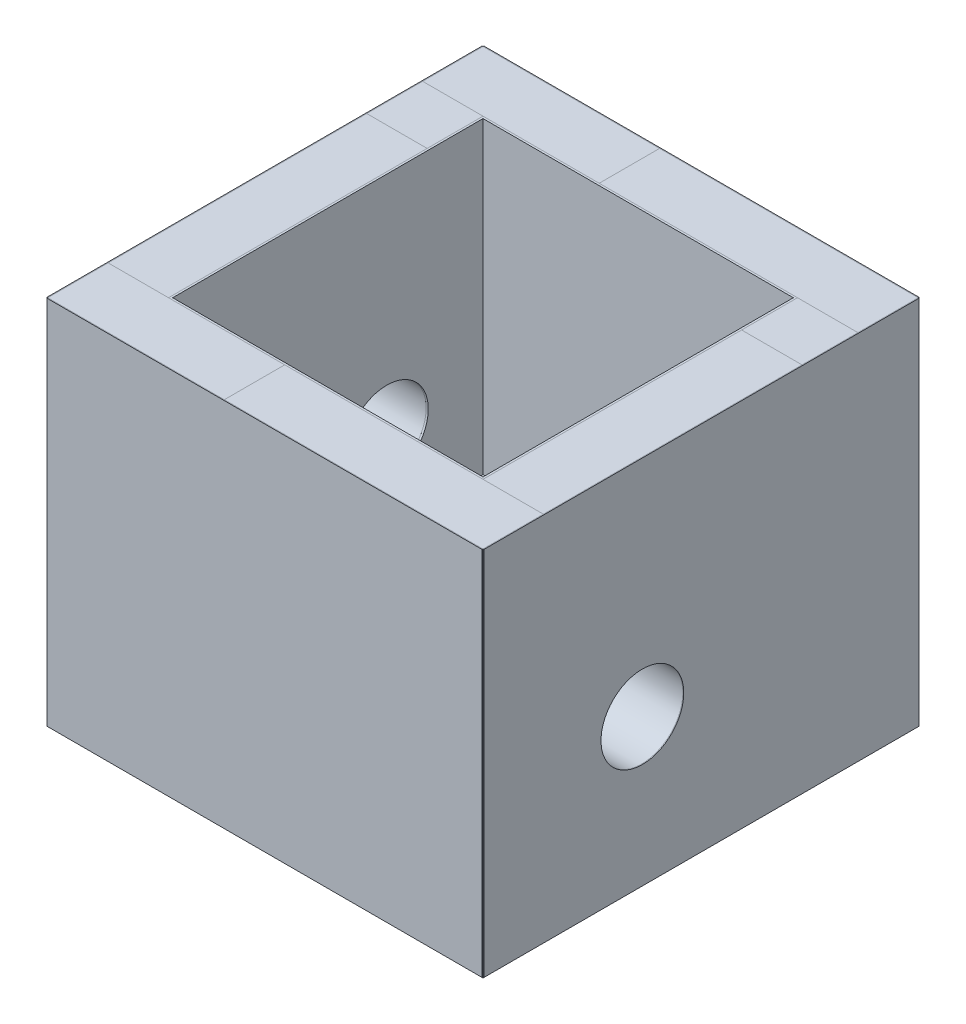
SolidWorks part; units mm, degrees
ref_plane "Front Plane" through (0, 0, 0) normal (0, 0, 1) x (1, 0, 0)
ref_plane "Top Plane" through (0, 0, 0) normal (0, 1, 0) x (1, 0, 0)
ref_plane "Right Plane" through (0, 0, 0) normal (1, 0, 0) x (0, 0, -1)
sketch "Sketch1" plane through (0, 0, 0) normal (0, 1, 0) x (1, 0, 0)
  line L1 (0, 0) -> (457.2, 0)
  line L2 (0, 0) -> (0, 457.2)
  line L3 (0, 457.2) -> (457.2, 457.2)
  line L4 (457.2, 0) -> (457.2, 457.2)
  dimension "D1" = 457.2
  dimension "D2" = 457.2
extrude "Boss-Extrude1" add sketch "Sketch1" along normal blind 3.048
sketch "Sketch2" plane through (0, 0, 0) normal (-1, 0, 0) x (0, 0, 1)
  line L1 (-457.2, 0) -> (0, 0)
  line L2 (-457.2, 0) -> (-457.2, 457.2)
  line L3 (-457.2, 457.2) -> (0, 457.2)
  line L4 (0, 0) -> (0, 457.2)
  dimension "D1" = 457.2
extrude "Boss-Extrude2" add sketch "Sketch2" along normal blind 3.048
sketch "Sketch3" plane through (0, 0, 0) normal (0, 0, 1) x (1, 0, 0)
  line L0 (457.2, 3.048) -> (457.2, 0) construction
  line L1 (-3.048, 0) -> (457.2, 0)
  line L2 (-3.048, 0) -> (-3.048, 457.2)
  line L3 (-3.048, 457.2) -> (457.2, 457.2)
  line L4 (457.2, 0) -> (457.2, 457.2)
  line L5 (-3.048, 457.2) -> (0, 457.2) construction
extrude "Boss-Extrude3" add sketch "Sketch3" along normal blind 3.048
sketch "Sketch4" plane through (457.2, 0, 0) normal (1, 0, 0) x (0, 0, -1)
  line L0 (457.2, 457.2) -> (457.2, 3.048) construction
  line L1 (-3.048, 0) -> (457.2, 0)
  line L2 (-3.048, 0) -> (-3.048, 457.2)
  line L3 (-3.048, 457.2) -> (457.2, 457.2)
  line L4 (457.2, 0) -> (457.2, 457.2)
  line L6 (-3.048, 0) -> (457.2, 0)
  line L7 (457.2, 0) -> (457.2, 3.048)
  line L8 (457.2, 3.048) -> (0, 3.048)
  line L9 (0, 3.048) -> (0, 457.2)
  line L10 (0, 457.2) -> (-3.048, 457.2)
  line L11 (-3.048, 457.2) -> (-3.048, 0)
  line L12 (-3.048, 0) -> (457.2, 0)
  line L13 (457.2, 0) -> (457.2, 3.048)
  line L14 (457.2, 3.048) -> (0, 3.048)
  line L15 (0, 3.048) -> (0, 457.2)
  line L16 (0, 457.2) -> (-3.048, 457.2)
  line L17 (-3.048, 457.2) -> (-3.048, 0)
  line M7 (-3.048, 0) -> (457.2, 0)
  line M8 (457.2, 0) -> (457.2, 3.048)
  line M9 (457.2, 3.048) -> (0, 3.048)
  line M10 (0, 3.048) -> (0, 457.2)
  line M11 (0, 457.2) -> (-3.048, 457.2)
  line M12 (-3.048, 457.2) -> (-3.048, 0)
  dimension "D1" = 0
extrude "Boss-Extrude4" add sketch "Sketch4" along normal blind 3.048 contours M12 M7 M8 M9 M10 M11 | L4 L3 M9 M10 region at (457.2, 228.6, 2.3993) region at (457.2, 230.124, -228.6)
sketch "Sketch5" plane through (0, 0, -457.2) normal (0, 0, -1) x (-1, 0, 0)
  line L1 (-460.248, 0) -> (3.048, 0)
  line L2 (-460.248, 0) -> (-460.248, 457.2)
  line L3 (-460.248, 457.2) -> (3.048, 457.2)
  line L4 (3.048, 0) -> (3.048, 457.2)
  line L8 (-460.248, 0) -> (3.048, 0)
  line L9 (3.048, 0) -> (3.048, 457.2)
  line L10 (3.048, 457.2) -> (0, 457.2)
  line L11 (0, 457.2) -> (0, 3.048)
  line L12 (0, 3.048) -> (-457.2, 3.048)
  line L13 (-457.2, 3.048) -> (-457.2, 457.2)
  line L14 (-457.2, 457.2) -> (-460.248, 457.2)
  line L15 (-460.248, 457.2) -> (-460.248, 0)
  line L16 (-460.248, 0) -> (3.048, 0)
  line L17 (3.048, 0) -> (3.048, 457.2)
  line L18 (3.048, 457.2) -> (0, 457.2)
  line L19 (0, 457.2) -> (0, 3.048)
  line L20 (0, 3.048) -> (-457.2, 3.048)
  line L21 (-457.2, 3.048) -> (-457.2, 457.2)
  line L23 (-460.248, 457.2) -> (-460.248, 0)
  line L28 (-457.2, 457.2) -> (-460.248, 457.2)
  line M9 (-460.248, 0) -> (3.048, 0)
  line M10 (3.048, 0) -> (3.048, 457.2)
  line M11 (3.048, 457.2) -> (0, 457.2)
  line M12 (0, 457.2) -> (0, 3.048)
  line M13 (0, 3.048) -> (-457.2, 3.048)
  line M14 (-457.2, 3.048) -> (-457.2, 457.2)
  line M15 (-457.2, 457.2) -> (-460.248, 457.2)
  line M16 (-460.248, 457.2) -> (-460.248, 0)
  dimension "D1" = 0
extrude "Boss-Extrude5" add sketch "Sketch5" along normal blind 3.048 contours L3 M14 M13 M12 | M16 M9 M10 M11 M12 M13 M14 M15 region at (459.5971, 228.6, -457.2) region at (228.6, 230.124, -457.2)
ref_plane "Plane1" through (228.6, 0, 0) normal (1, 0, 0) x (0, 0, -1)
sketch "Sketch6" plane through (460.248, 0, 0) normal (1, 0, 0) x (0, 0, -1)
  line L1 (-3.048, 457.2) -> (377.952, 457.2)
  line L2 (-3.048, 457.2) -> (-3.048, 0)
  line L3 (-3.048, 0) -> (377.952, 0)
  line L4 (-3.048, 457.2) -> (-3.048, 0)
  line L5 (-3.048, 0) -> (460.248, 0)
  line L6 (460.248, 0) -> (460.248, 457.2)
  line L7 (460.248, 457.2) -> (-3.048, 457.2)
  line L8 (-3.048, 457.2) -> (-3.048, 0)
  line L9 (-3.048, 0) -> (460.248, 0)
  line L10 (460.248, 0) -> (460.248, 457.2)
  line L11 (460.248, 457.2) -> (-3.048, 457.2)
  line L12 (377.952, 457.2) -> (377.952, 0)
  line L13 (460.248, 0) -> (377.952, 0)
  line L14 (460.248, 0) -> (460.248, 381)
  line L15 (460.248, 381) -> (377.952, 381)
  line L16 (377.952, 0) -> (377.952, 381)
  line L17 (377.952, 381) -> (460.248, 381)
  line L18 (377.952, 381) -> (377.952, 457.2)
  line L19 (377.952, 457.2) -> (460.248, 457.2)
  line L20 (460.248, 381) -> (460.248, 457.2)
  line M10 (-3.048, 457.2) -> (-3.048, 0)
  line M11 (-3.048, 0) -> (460.248, 0)
  line M12 (460.248, 0) -> (460.248, 457.2)
  line M13 (460.248, 457.2) -> (-3.048, 457.2)
  dimension "D2" = 381
  dimension "D3" = 381
  dimension "D1" = 0
extrude "Boss-Extrude6" add sketch "Sketch6" along normal blind 88.9 separate body contours L12 M13 M10 M11 region at (460.248, 228.6, -187.452)
extrude "Boss-Extrude7" add sketch "Sketch6<3>" along normal blind 88.9 separate body contours L15 L10 L12 M13 region at (460.248, 419.1, -419.1)
sketch "Sketch6<3>" plane through (460.248, 0, 0) normal (1, 0, 0) x (0, 0, -1) same geometry as "Sketch6"
extrude "Boss-Extrude8" add sketch "Sketch6<4>" along normal blind 88.9 separate body contours L15 L12 M12 M11 region at (460.248, 190.5, -419.1)
sketch "Sketch6<4>" plane through (460.248, 0, 0) normal (1, 0, 0) x (0, 0, -1) same geometry as "Sketch6"
mirror "Mirror1" about plane through (228.6, 0, 0) normal (1, 0, 0) of bodies 116 115 117
sketch "Sketch7" plane through (0, 0, -460.248) normal (0, 0, -1) x (-1, 0, 0)
  line L0 (-460.248, 0) -> (3.048, 0) construction
  line L1 (-549.148, 457.2) -> (-168.148, 457.2)
  line L2 (-549.148, 457.2) -> (-549.148, 0)
  line L3 (-549.148, 0) -> (-168.148, 0)
  line L4 (-168.148, 457.2) -> (-168.148, 0)
  line L5 (91.948, 381) -> (91.948, 457.2) construction
  line L6 (-168.148, 457.2) -> (91.948, 457.2)
  line L7 (-168.148, 457.2) -> (-168.148, 76.2)
  line L8 (-168.148, 76.2) -> (91.948, 76.2)
  line L9 (91.948, 457.2) -> (91.948, 76.2)
  line L11 (-168.148, 76.2) -> (91.948, 76.2)
  line L12 (-168.148, 76.2) -> (-168.148, 0)
  line L13 (-168.148, 0) -> (91.948, 0)
  line L14 (91.948, 76.2) -> (91.948, 0)
  line M9 (-460.248, 0) -> (-460.248, 381)
  line M10 (-460.248, 381) -> (-549.148, 381)
  line M11 (-549.148, 381) -> (-549.148, 0)
  line M12 (-549.148, 0) -> (-460.248, 0)
  dimension "D1" = 381
  dimension "D3" = 381
extrude "Boss-Extrude9" add sketch "Sketch7" along normal blind 88.9 separate body contours L4 L1 L2 L3 M10 M9 | M12 M9 M10 M11 region at (323.3946, 237.7966, -460.248) region at (504.698, 190.5, -460.248)
extrude "Boss-Extrude10" add sketch "Sketch7<3>" along normal blind 88.9 separate body contours L9 L6 L4 L8 region at (38.1, 266.7, -460.248)
sketch "Sketch7<3>" plane through (0, 0, -460.248) normal (0, 0, -1) x (-1, 0, 0) same geometry as "Sketch7"
extrude "Boss-Extrude11" add sketch "Sketch7<4>" along normal blind 88.9 separate body contours L14 L8 L4 L13 region at (38.1, 38.1, -460.248)
sketch "Sketch7<4>" plane through (0, 0, -460.248) normal (0, 0, -1) x (-1, 0, 0) same geometry as "Sketch7"
ref_plane "Plane2" through (0, 0, -228.6) normal (0, 0, -1) x (-1, 0, 0)
mirror "Mirror2" about plane through (0, 0, -228.6) normal (0, 0, -1) of bodies 122 121 123
sketch "Sketch8" plane through (0, 0, 0) normal (0, -1, 0) x (1, 0, 0)
  line L0 (549.148, -549.148) -> (168.148, -549.148) construction
  line L1 (-91.948, 91.948) -> (289.052, 91.948)
  line L2 (-91.948, 91.948) -> (-91.948, -549.148)
  line L3 (-91.948, -549.148) -> (289.052, -549.148)
  line L4 (289.052, 91.948) -> (289.052, -549.148)
  line L5 (549.148, 3.048) -> (549.148, -377.952) construction
  line L6 (289.052, 91.948) -> (549.148, 91.948)
  line L7 (289.052, 91.948) -> (289.052, -289.052)
  line L8 (289.052, -289.052) -> (549.148, -289.052)
  line L9 (549.148, 91.948) -> (549.148, -289.052)
  line L11 (289.052, -289.052) -> (549.148, -289.052)
  line L12 (289.052, -289.052) -> (289.052, -549.148)
  line L13 (289.052, -549.148) -> (549.148, -549.148)
  line L14 (549.148, -289.052) -> (549.148, -549.148)
  line M7 (-3.048, 3.048) -> (-3.048, -460.248)
  line M8 (-3.048, -460.248) -> (460.248, -460.248)
  line M9 (460.248, -460.248) -> (460.248, 3.048)
  line M10 (460.248, 3.048) -> (-3.048, 3.048)
  dimension "D1" = 381
  dimension "D2" = 381
extrude "Boss-Extrude12" add sketch "Sketch8" along normal blind 88.9 separate body contours L4 M10 M7 M8 | L4 L1 L2 L3 M8 M7 M10 region at (98.552, 0, 84.4904) region at (143.002, 0, -228.6)
extrude "Boss-Extrude13" add sketch "Sketch8<3>" along normal blind 88.9 separate body contours L4 L8 M9 M10 | L9 L6 L4 L8 M10 M9 region at (464.3795, 0, -53.2725) region at (374.65, 0, -143.002)
sketch "Sketch8<3>" plane through (0, 0, 0) normal (0, -1, 0) x (1, 0, 0) same geometry as "Sketch8"
extrude "Boss-Extrude14" add sketch "Sketch8<4>" along normal blind 88.9 separate body contours L8 L4 M8 M9 | L14 L8 L4 L13 M9 M8 region at (374.65, 0, -374.65) region at (292.7303, 0, -504.698)
sketch "Sketch8<4>" plane through (0, 0, 0) normal (0, -1, 0) x (1, 0, 0) same geometry as "Sketch8"
sketch "Sketch9" plane through (549.148, 0, 0) normal (1, 0, 0) x (0, 0, -1)
  line L1 (-91.948, 457.2) -> (549.148, 457.2)
  line L2 (-91.948, 457.2) -> (-91.948, -88.9)
  line L3 (-91.948, -88.9) -> (549.148, -88.9)
  line L4 (549.148, 457.2) -> (549.148, -88.9)
extrude "Boss-Extrude15" add sketch "Sketch9" along normal blind 1.2192 separate body
sketch "Sketch10" plane through (0, 0, -549.148) normal (0, 0, -1) x (-1, 0, 0)
  line L1 (-549.148, 457.2) -> (91.948, 457.2)
  line L2 (-549.148, 457.2) -> (-549.148, -88.9)
  line L3 (-549.148, -88.9) -> (91.948, -88.9)
  line L4 (91.948, 457.2) -> (91.948, -88.9)
extrude "Boss-Extrude16" add sketch "Sketch10" along normal blind 1.2192 separate body
mirror "Mirror3" about plane through (228.6, 0, 0) normal (1, 0, 0) of bodies 130
mirror "Mirror4" about plane through (0, 0, -228.6) normal (0, 0, -1) of bodies 131
sketch "Sketch11" plane through (0, -88.9, 0) normal (0, -1, 0) x (1, 0, 0)
  line L1 (-91.948, 91.948) -> (549.148, 91.948)
  line L2 (-91.948, 91.948) -> (-91.948, -549.148)
  line L3 (-91.948, -549.148) -> (549.148, -549.148)
  line L4 (549.148, 91.948) -> (549.148, -549.148)
extrude "Boss-Extrude17" add sketch "Sketch11" along normal blind 1.2192 separate body
sketch "Sketch12" plane through (-93.1672, 0, 0) normal (-1, 0, 0) x (0, 0, 1)
  line L4 (91.948, -88.9) -> (91.948, 457.2)
  line L5 (91.948, 457.2) -> (-549.148, 457.2)
  line L6 (-549.148, 457.2) -> (-549.148, -88.9)
  line L7 (-549.148, -88.9) -> (91.948, -88.9)
  line L8 (91.948, -88.9) -> (91.948, 457.2)
  line L9 (91.948, 457.2) -> (-549.148, 457.2)
  line L10 (-549.148, 457.2) -> (-549.148, -88.9)
  line L11 (-549.148, -88.9) -> (91.948, -88.9)
  circle A0 centre (-315.5938, 127) radius 60.96
  point P6 (-444.2871, 203.2)
  point P7 (-414.8099, 127)
  point P8 (-354.4175, 127)
  point P9 (-288.2734, 127)
  point P10 (-309.1232, 127)
  point P11 (-335.0056, 127)
  point P12 (-315.5938, 127)
  dimension "D2" = 330.2
  dimension "D3" = 121.92
  dimension "D1" = 0
extrude "Cut-Extrude1" cut sketch "Sketch12" against normal up to surface (550.3672 mm away) contours A0 region at (-93.1672, 127, -315.5938) up to face at (457.2, 230.124, -228.6)
ref_axis "Axis1" through (228.6, 479.9076, -228.6) along (0, -1, 0)
pattern_circular "CirPattern1" count 2 over 360 about axis through (228.6, 479.9076, -228.6) along (0, -1, 0) of "Cut-Extrude1"
